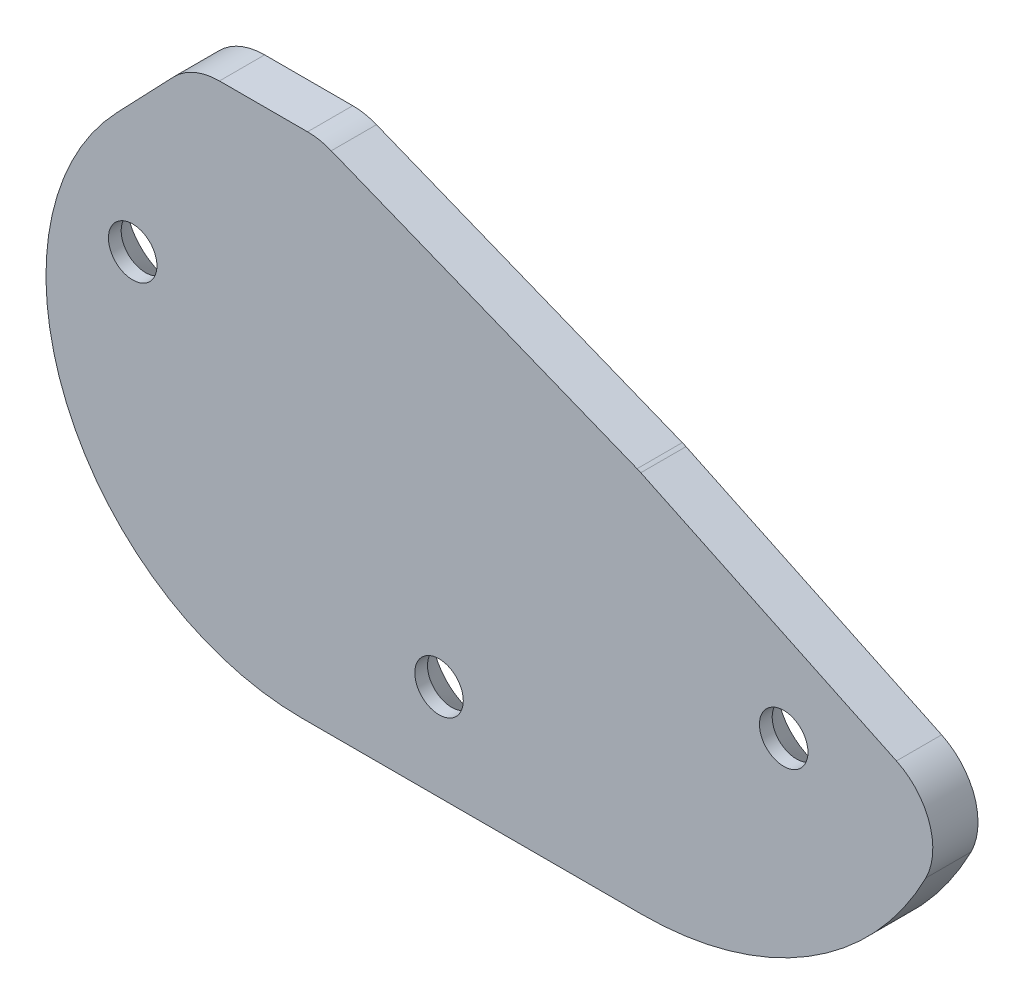
SolidWorks part; units mm, degrees
material "Titanium"
ref_plane "Front Plane" through (0, 0, 0) normal (0, 0, 1) x (1, 0, 0)
ref_plane "Top Plane" through (0, 0, 0) normal (0, 1, 0) x (1, 0, 0)
ref_plane "Right Plane" through (0, 0, 0) normal (1, 0, 0) x (0, 0, -1)
sketch "Sketch1" plane through (0, 0, 0) normal (0, 0, 1) x (1, 0, 0)
  line L0 (26.2421, 50.8) -> (0, 23.368)
  line L1 (26.2421, 50.8) -> (38.9421, 50.8)
  line L2 (38.9421, 50.8) -> (70.6921, 38.0905)
  line L3 (70.6921, 38.0905) -> (101.6, 23.368)
  line L4 (101.6, 23.368) -> (101.6, 0)
  line L5 (101.6, 0) -> (0, 0)
  line L6 (0, 23.368) -> (0, 0)
  circle A0 centre (20.32, 31.75) radius 2.413
  circle A1 centre (50.8, 9.525) radius 2.413
  circle A2 centre (85.09, 22.225) radius 2.413
  dimension "D8" = 4.826
  dimension "D1" = 12.7
  dimension "D2" = 23.368
  dimension "D3" = 25.47
  dimension "D4" = 31.75
  dimension "D5" = 46.27
  dimension "D6" = 50.8
  dimension "D7" = 101.6
  dimension "D9" = 9.525
  dimension "D10" = 30.48
  dimension "D11" = 34.29
  dimension "D12" = 12.7
  dimension "D13" = 50.8
  dimension "D14" = 22.225
extrude "Extrude1" add sketch "Sketch1" along normal blind 4.4958
sketch "Sketch2" plane through (0, 0, 4.4958) normal (0, 0, 1) x (1, 0, 0)
  line L0 (26.2421, 50.8) -> (0, 23.368) construction
  line L1 (0, 0) -> (101.6, 0) construction
  line L2 (18.7403, 42.958) -> (0, 23.368)
  line L3 (0, 23.368) -> (0, 0)
  line L4 (0, 0) -> (37.0944, 0)
  line L5 (101.6, 23.368) -> (101.6, 0)
  line L6 (101.6, 0) -> (70.9764, 0)
  arc A0 (18.7403, 42.958) -> (37.0944, 0) centre (37.0944, 25.4) ccw
  arc A1 (101.6, 23.368) -> (70.9764, 0) centre (70.9764, 31.75) cw
  dimension "D1" = 25.4
  dimension "D2" = 31.75
extrude "Cut-Extrude1" cut sketch "Sketch2" against normal through all
fillet "Fillet1" radius 6.35 4 edges at (26.2421, 50.8, 2.2479) (38.9421, 50.8, 2.2479) (70.6921, 38.0905, 2.2479) (101.6, 23.368, 2.2479)
sketch "Sketch4" plane through (0, 0, 0) normal (0, 0, -1) x (-1, 0, 0)
  circle A0 centre (-20.32, 31.75) radius 5.2197
  circle A1 centre (-50.8, 9.525) radius 5.2197
  circle A2 centre (-85.09, 22.225) radius 5.2197
  dimension "D1" = 10.4394
extrude "Cut-Extrude2" cut sketch "Sketch4" against normal through all draft 41
